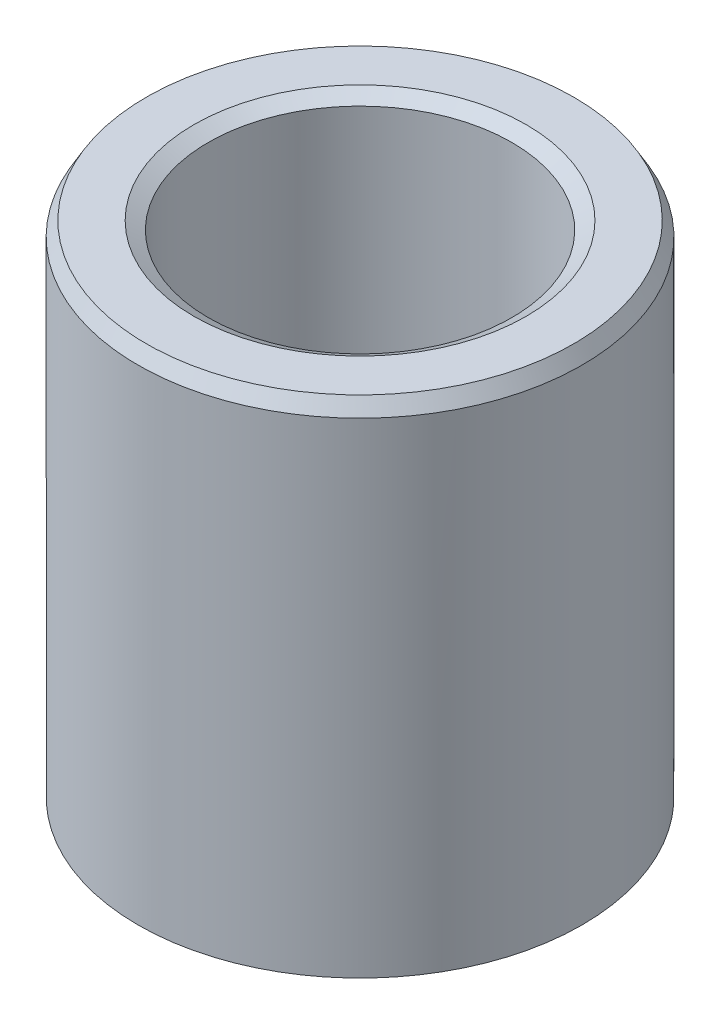
SolidWorks part; units mm, degrees
ref_plane "Front Plane" through (0, 0, 0) normal (0, 0, 1) x (1, 0, 0)
ref_plane "Top Plane" through (0, 0, 0) normal (0, 1, 0) x (1, 0, 0)
ref_plane "Right Plane" through (0, 0, 0) normal (1, 0, 0) x (0, 0, -1)
sketch "Sketch1" plane through (0, 0, 0) normal (0, 1, 0) x (1, 0, 0)
  circle A0 centre (0, 0) radius 45
  dimension "SLEEVE_OD" = 90
extrude "Boss-Extrude1" add sketch "Sketch1" along normal blind 102.8788
sketch "Sketch2" plane through (0, 0, 0) normal (0, 1, 0) x (1, 0, 0)
  circle A0 centre (0, 0) radius 30.7752
  dimension "BORE_D" = 61.5503
extrude "Cut-Extrude1" cut sketch "Sketch2" along normal through all
chamfer "Chamfer1" distance 2.9032 angle 30 4 edges at (0, 102.8788, 30.7752) (0, 0, 30.7752) (0, 0, 45) (0, 102.8788, 45) first distance on face at (0, 102.8788, 30.7752) first distance on face at (0, 0, 30.7752) first distance on face at (0, 102.8788, 45)
